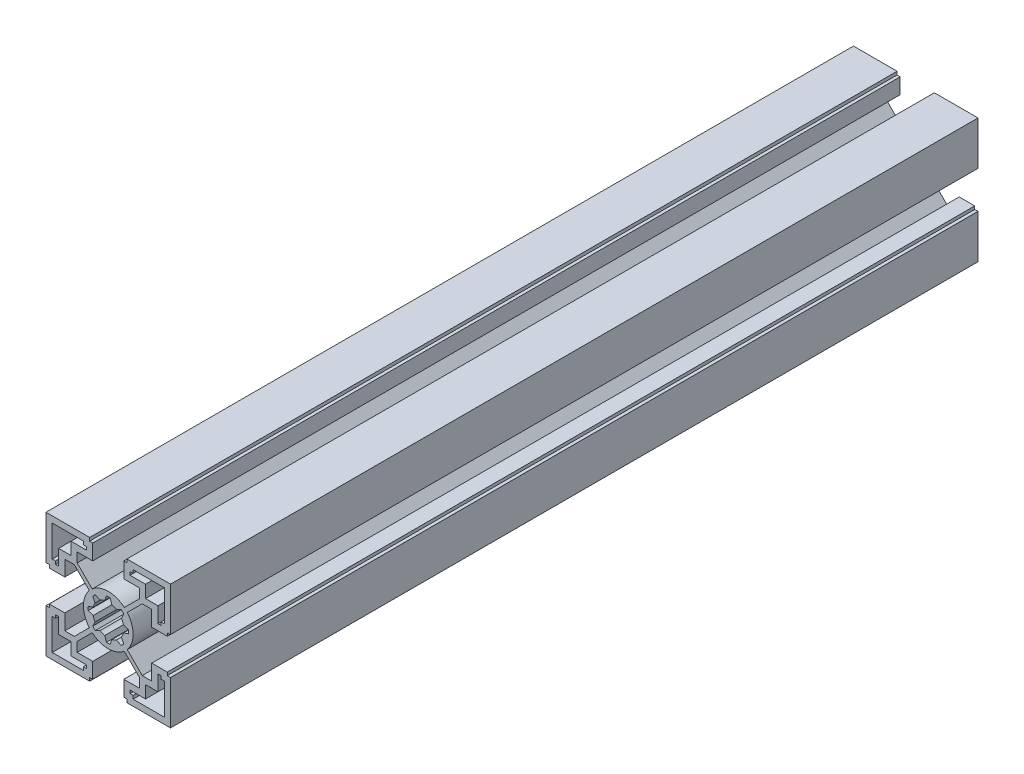
SolidWorks part; units mm, degrees
material "Aleación 2024"
ref_plane "Alzado" through (0, 0, 0) normal (0, 0, 1) x (1, 0, 0)
ref_plane "Planta" through (0, 0, 0) normal (0, 1, 0) x (1, 0, 0)
ref_plane "Vista lateral" through (0, 0, 0) normal (1, 0, 0) x (0, 0, -1)
sketch "Croquis1" plane through (0, 0, 0) normal (0, 0, 1) x (1, 0, 0)
  line L0 (-0.5883, 6.4733) -> (-1.1436, 4.8675)
  line L1 (0, 0) -> (-20, 0) construction
  line L2 (-20, 6) -> (-20, -6)
  line L3 (0.5883, 6.4733) -> (1.1436, 4.8675)
  line L4 (4.1614, 4.9933) -> (2.6332, 4.2504)
  line L5 (4.9933, 4.1614) -> (4.2504, 2.6332)
  line L6 (-20, 6) -> (-19, 6)
  line L7 (6.4733, 0.5883) -> (4.8675, 1.1436)
  line L8 (6.4733, -0.5883) -> (4.8675, -1.1436)
  line L9 (-14, 5) -> (-14, 10)
  line L10 (4.9933, -4.1614) -> (4.2504, -2.6332)
  line L11 (4.1614, -4.9933) -> (2.6332, -4.2504)
  line L12 (-6.101, 5.1747) -> (-10.9263, 10)
  line L13 (0.5883, -6.4733) -> (1.1436, -4.8675)
  line L14 (-0.5883, -6.4733) -> (-1.1436, -4.8675)
  line L15 (-14, 10) -> (-10.9263, 10)
  line L16 (-4.1614, -4.9933) -> (-2.6332, -4.2504)
  line L17 (-4.9933, -4.1614) -> (-4.2504, -2.6332)
  line L18 (-19, 5) -> (-14, 5)
  line L19 (-6.4733, -0.5883) -> (-4.8675, -1.1436)
  line L20 (-6.4733, 0.5883) -> (-4.8675, 1.1436)
  line L21 (-19, 6) -> (-19, 5)
  line L22 (-4.9933, 4.1614) -> (-4.2504, 2.6332)
  line L23 (-4.1614, 4.9933) -> (-2.6332, 4.2504)
  line L24 (-19, -6) -> (-19, -5)
  line L25 (-20, -6) -> (-19, -6)
  line L26 (-19, -5) -> (-14, -5)
  line L27 (-14, -5) -> (-14, -10)
  line L28 (-14, -10) -> (-10.9263, -10)
  line L29 (-6.101, -5.1747) -> (-10.9263, -10)
  arc A0 (-1.1436, 4.8675) -> (-2.6332, 4.2504) centre (0, 0) ccw
  arc A1 (-6.101, 5.1747) -> (-6.101, -5.1747) centre (0, 0) ccw
  arc A2 (-4.9933, -4.1614) -> (-4.1614, -4.9933) centre (0, 0) ccw
  arc A3 (-4.2504, 2.6332) -> (-4.8675, 1.1436) centre (0, 0) ccw
  arc A4 (-4.8675, -1.1436) -> (-4.2504, -2.6332) centre (0, 0) ccw
  arc A5 (-2.6332, -4.2504) -> (-1.1436, -4.8675) centre (0, 0) ccw
  arc A6 (1.1436, -4.8675) -> (2.6332, -4.2504) centre (0, 0) ccw
  arc A7 (4.2504, -2.6332) -> (4.8675, -1.1436) centre (0, 0) ccw
  arc A8 (4.8675, 1.1436) -> (4.2504, 2.6332) centre (0, 0) ccw
  arc A9 (2.6332, 4.2504) -> (1.1436, 4.8675) centre (0, 0) ccw
  arc A10 (-6.4733, 0.5883) -> (-6.4733, -0.5883) centre (0, 0) ccw
  arc A11 (-4.1614, 4.9933) -> (-4.9933, 4.1614) centre (0, 0) ccw
  arc A12 (-0.5883, -6.4733) -> (0.5883, -6.4733) centre (0, 0) ccw
  arc A13 (4.1614, -4.9933) -> (4.9933, -4.1614) centre (0, 0) ccw
  arc A14 (6.4733, -0.5883) -> (6.4733, 0.5883) centre (0, 0) ccw
  arc A15 (4.9933, 4.1614) -> (4.1614, 4.9933) centre (0, 0) ccw
  arc A16 (0.5883, 6.4733) -> (-0.5883, 6.4733) centre (0, 0) ccw
  point P42 (0, 0)
  dimension "D1" = 10
  dimension "D2" = 16
  dimension "D3" = 13
  dimension "D4" = 8
sketch "Croquis2" plane through (0, 0, 0) normal (0, 0, 1) x (1, 0, 0)
  line L1 (-20.05, -20.05) -> (20.05, -20.05)
  line L2 (-20.05, -20.05) -> (-20.05, 20.05)
  line L3 (-20.05, 20.05) -> (20.05, 20.05)
  line L4 (20.05, -20.05) -> (20.05, 20.05)
  line L5 (-20.05, -20.05) -> (20.05, 20.05) construction
  line L6 (-20.05, 20.05) -> (20.05, -20.05) construction
  point P0 (0, 0)
  dimension "altura" = 40.1
  dimension "ancho" = 40.1
extrude "Saliente-Extruir1" add sketch "Croquis2" against normal blind 260
sketch "Croquis3" plane through (0, 0, 0) normal (0, 0, 1) x (1, 0, 0)
  line L0 (-0.5883, 6.4733) -> (-1.1436, 4.8675)
  line L1 (0, 0) -> (-20, 0) construction
  line L2 (-20, 6) -> (-20, -6)
  line L3 (0.5883, 6.4733) -> (1.1436, 4.8675)
  line L4 (4.1614, 4.9933) -> (2.6332, 4.2504)
  line L5 (4.9933, 4.1614) -> (4.2504, 2.6332)
  line L6 (-20, 6) -> (-19, 6)
  line L7 (6.4733, 0.5883) -> (4.8675, 1.1436)
  line L8 (6.4733, -0.5883) -> (4.8675, -1.1436)
  line L9 (-14, 5) -> (-14, 10)
  line L10 (4.9933, -4.1614) -> (4.2504, -2.6332)
  line L11 (4.1614, -4.9933) -> (2.6332, -4.2504)
  line L12 (-6.101, 5.1747) -> (-10.9263, 10)
  line L13 (0.5883, -6.4733) -> (1.1436, -4.8675)
  line L14 (-0.5883, -6.4733) -> (-1.1436, -4.8675)
  line L15 (-14, 10) -> (-10.9263, 10)
  line L16 (-4.1614, -4.9933) -> (-2.6332, -4.2504)
  line L17 (-4.9933, -4.1614) -> (-4.2504, -2.6332)
  line L18 (-19, 5) -> (-14, 5)
  line L19 (-6.4733, -0.5883) -> (-4.8675, -1.1436)
  line L20 (-6.4733, 0.5883) -> (-4.8675, 1.1436)
  line L21 (-19, 6) -> (-19, 5)
  line L22 (-4.9933, 4.1614) -> (-4.2504, 2.6332)
  line L23 (-4.1614, 4.9933) -> (-2.6332, 4.2504)
  line L24 (-19, -6) -> (-19, -5)
  line L25 (-20, -6) -> (-19, -6)
  line L26 (-19, -5) -> (-14, -5)
  line L27 (-14, -5) -> (-14, -10)
  line L28 (-14, -10) -> (-10.9263, -10)
  line L29 (-6.101, -5.1747) -> (-10.9263, -10)
  arc A0 (-1.1436, 4.8675) -> (-2.6332, 4.2504) centre (0, 0) ccw
  arc A1 (-6.101, 5.1747) -> (-6.101, -5.1747) centre (0, 0) ccw
  arc A2 (-4.9933, -4.1614) -> (-4.1614, -4.9933) centre (0, 0) ccw
  arc A3 (-4.2504, 2.6332) -> (-4.8675, 1.1436) centre (0, 0) ccw
  arc A4 (-4.8675, -1.1436) -> (-4.2504, -2.6332) centre (0, 0) ccw
  arc A5 (-2.6332, -4.2504) -> (-1.1436, -4.8675) centre (0, 0) ccw
  arc A6 (1.1436, -4.8675) -> (2.6332, -4.2504) centre (0, 0) ccw
  arc A7 (4.2504, -2.6332) -> (4.8675, -1.1436) centre (0, 0) ccw
  arc A8 (4.8675, 1.1436) -> (4.2504, 2.6332) centre (0, 0) ccw
  arc A9 (2.6332, 4.2504) -> (1.1436, 4.8675) centre (0, 0) ccw
  arc A10 (-6.4733, 0.5883) -> (-6.4733, -0.5883) centre (0, 0) ccw
  arc A11 (-4.1614, 4.9933) -> (-4.9933, 4.1614) centre (0, 0) ccw
  arc A12 (-0.5883, -6.4733) -> (0.5883, -6.4733) centre (0, 0) ccw
  arc A13 (4.1614, -4.9933) -> (4.9933, -4.1614) centre (0, 0) ccw
  arc A14 (6.4733, -0.5883) -> (6.4733, 0.5883) centre (0, 0) ccw
  arc A15 (4.9933, 4.1614) -> (4.1614, 4.9933) centre (0, 0) ccw
  arc A16 (0.5883, 6.4733) -> (-0.5883, 6.4733) centre (0, 0) ccw
  point P42 (0, 0)
extrude "Cortar-Extruir1" cut sketch "Croquis3" against normal through all
ref_axis "Eje1" through (0, 0, -260) along (0, 0, 1)
pattern_circular "MatrizC1" count 4 every 90 about axis through (0, 0, -260) along (0, 0, 1) of "Cortar-Extruir1" reverse direction yes
shell "Vaciado1" thickness 2 removed face at (0, 14.8538, -260) removed face at (0, 14.8538, 0)
sketch "Croquis4" plane through (0, 0, 0) normal (0, 0, 1) x (1, 0, 0)
  line L0 (20.05, 20.05) -> (-20.05, 20.05) construction
  line L1 (-6, 20) -> (6.0001, 20)
  line L2 (-6, 20) -> (-6, 20.05)
  line L3 (-6, 20.05) -> (6.0001, 20.05)
  line L4 (6.0001, 20) -> (6.0001, 20.05)
  line L5 (20, 6) -> (20.05, 6)
  line L6 (20.05, 6) -> (20.05, -6.0001)
  line L7 (20, 6) -> (20, -6.0001)
  line L8 (20, -6.0001) -> (20.05, -6.0001)
  line L9 (6, -20) -> (6, -20.05)
  line L10 (6, -20.05) -> (-6.0001, -20.05)
  line L11 (6, -20) -> (-6.0001, -20)
  line L12 (-6.0001, -20) -> (-6.0001, -20.05)
  line L13 (-20, -6) -> (-20.05, -6)
  line L14 (-20.05, -6) -> (-20.05, 6.0001)
  line L15 (-20, -6) -> (-20, 6.0001)
  line L16 (-20, 6.0001) -> (-20.05, 6.0001)
  point P22 (0, 0)
  dimension "D1" = 4
extrude "Cortar-Extruir2" cut sketch "Croquis4" against normal through all
